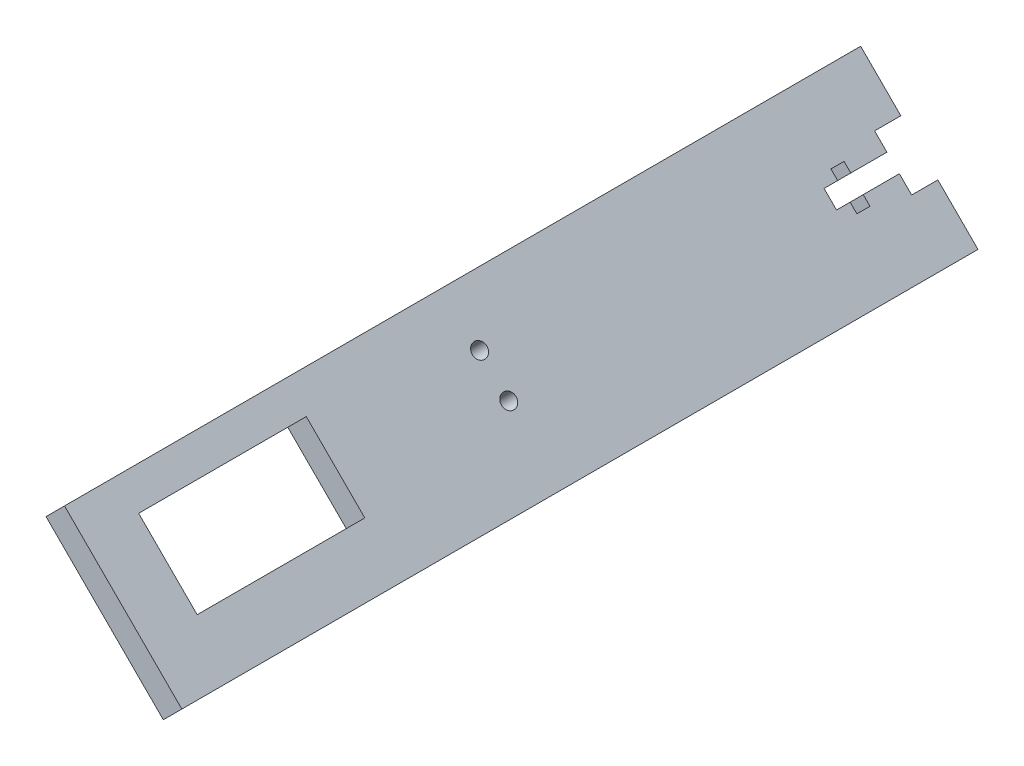
SolidWorks part; units mm, degrees
ref_plane "Front Plane" through (0, 0, 0) normal (0, 0, 1) x (1, 0, 0)
ref_plane "Top Plane" through (0, 0, 0) normal (0, 1, 0) x (1, 0, 0)
ref_plane "Right Plane" through (0, 0, 0) normal (1, 0, 0) x (0, 0, -1)
sketch "Sketch2" plane through (0, 0, 0) normal (0, 0, 1) x (1, 0, 0)
  line L0 (-71.1005, -144.0441) -> (-75.5906, -148.5343)
  line L1 (-71.1005, -144.0441) -> (-42.6562, -172.4884)
  line L2 (-75.5906, -148.5343) -> (-47.1463, -176.9785)
  line L3 (-42.6562, -172.4884) -> (-47.1463, -176.9785)
  line L4 (-75.5906, -148.5343) -> (-65.8586, -158.2663) construction
  line L5 (-61.3685, -153.7761) -> (-71.1005, -144.0441) construction
  line L6 (-47.1463, -176.9785) -> (-42.6562, -172.4884) construction
  line L7 (-71.1005, -144.0441) -> (-75.5906, -148.5343) construction
extrude "Boss-Extrude1" add sketch "Sketch2" along normal blind 186.69
sketch "Sketch3" plane through (-112.0624, -112.0624, 0) normal (-0.7071, -0.7071, 0) x (0, 0, 1)
  line L0 (0, -71.6921) -> (24.1393, -71.6921) construction
  line L1 (0, -51.579) -> (0, -91.8052) construction
  line B0 (0, -69.5585) -> (0, -73.8257)
  line B1 (11.938, -73.8257) -> (11.938, -76.1371)
  line B2 (11.938, -76.1371) -> (8.763, -76.1371)
  line B3 (8.763, -76.1371) -> (8.763, -73.8257)
  line B4 (8.763, -73.8257) -> (0, -73.8257)
  line B5 (11.938, -73.8257) -> (15.24, -73.8257)
  line B6 (15.24, -73.8257) -> (15.24, -69.5585)
  line B7 (11.938, -69.5585) -> (15.24, -69.5585)
  line B8 (8.763, -69.5585) -> (0, -69.5585)
  line B9 (8.763, -67.2471) -> (8.763, -69.5585)
  line B10 (11.938, -67.2471) -> (8.763, -67.2471)
  line B11 (11.938, -69.5585) -> (11.938, -67.2471)
sketch_block_instance "TSlot-1"
sketch_block "TSlot" parameters "D1"=3.302, "D2"=3.175
extrude "Cut-Extrude1" cut sketch "Sketch3" against normal through all
sketch "Sketch4" plane through (0, 0, 0) normal (0, 0, -1) x (-1, 0, 0)
  line L0 (75.5906, -148.5343) -> (65.8586, -158.2663) construction
  line L1 (65.8586, -158.2663) -> (61.3685, -153.7761) construction
  line L2 (61.3685, -153.7761) -> (71.1005, -144.0441) construction
  line L3 (71.1005, -144.0441) -> (75.5906, -148.5343) construction
  line L4 (42.6562, -172.4884) -> (52.3882, -162.7564) construction
  line L5 (52.3882, -162.7564) -> (56.8783, -167.2465) construction
  line L6 (56.8783, -167.2465) -> (47.1463, -176.9785) construction
  line L7 (47.1463, -176.9785) -> (42.6562, -172.4884) construction
  line L8 (75.5906, -148.5343) -> (65.8586, -158.2663)
  line L9 (65.8586, -158.2663) -> (61.3685, -153.7761)
  line L10 (61.3685, -153.7761) -> (71.1005, -144.0441)
  line L11 (71.1005, -144.0441) -> (75.5906, -148.5343)
  line L12 (42.6562, -172.4884) -> (52.3882, -162.7564)
  line L13 (52.3882, -162.7564) -> (56.8783, -167.2465)
  line L14 (56.8783, -167.2465) -> (47.1463, -176.9785)
  line L15 (47.1463, -176.9785) -> (42.6562, -172.4884)
extrude "Boss-Extrude2" add sketch "Sketch4" along normal blind 6.35
sketch "Sketch5" plane through (-107.5723, -107.5723, 0) normal (0.7071, 0.7071, 0) x (0, 0, -1)
  line L1 (-173.99, -59.0392) -> (-133.35, -59.0392)
  line L2 (-173.99, -59.0392) -> (-173.99, -79.1052)
  line L3 (-173.99, -79.1052) -> (-133.35, -79.1052)
  line L4 (-133.35, -59.0392) -> (-133.35, -79.1052)
  line L5 (-186.69, -91.8052) -> (-186.69, -51.579) construction
  line L6 (-165.1552, -59.0392) -> (-139.1365, -59.0392) construction
  line L7 (-139.1365, -79.1052) -> (-164.2745, -79.1052) construction
  line L8 (-165.1552, -59.0392) -> (-139.1365, -59.0392) construction
  line L9 (-139.1365, -79.1052) -> (-164.2745, -79.1052) construction
  dimension "D1" = 40.64
  dimension "D2" = 12.7
extrude "Cut-Extrude2" cut sketch "Sketch5" against normal through all
sketch "Sketch6" plane through (-107.5723, -107.5723, 0) normal (0.7071, 0.7071, 0) x (0, 0, -1)
  circle A8 centre (-143.88, -64.0722) radius 1.778
  circle A9 centre (-143.88, -74.0722) radius 1.778
  circle A10 centre (-94.88, -64.0722) radius 1.778
  circle A11 centre (-94.88, -74.0722) radius 1.778
extrude "Cut-Extrude3" cut sketch "Sketch6" against normal through all
